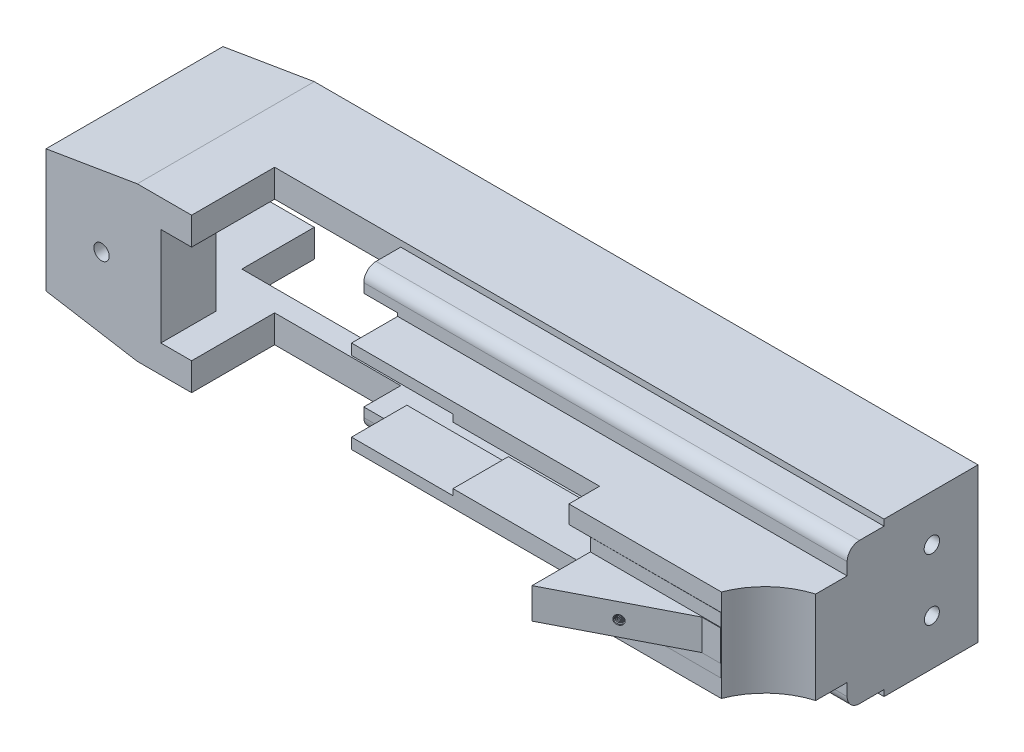
SolidWorks part; units mm, degrees
ref_plane "Front Plane" through (0, 0, 0) normal (0, 0, 1) x (1, 0, 0)
ref_plane "Top Plane" through (0, 0, 0) normal (0, 1, 0) x (1, 0, 0)
ref_plane "Right Plane" through (0, 0, 0) normal (1, 0, 0) x (0, 0, -1)
sketch "Sketch1" plane through (0, 0, 0) normal (0, 0, 1) x (1, 0, 0)
  line L0 (0, 0) -> (245.5, 0)
  line L1 (245.5, 0) -> (245.5, 50)
  line L2 (245.5, 50) -> (0, 50)
  line L3 (0, 50) -> (0, 0)
  dimension "D1" = 245.5
  dimension "D2" = 50
extrude "Boss-Extrude1" add sketch "Sketch1" along normal blind 57.55
sketch "Sketch2" plane through (0, 0, 0) normal (0, 0, -1) x (-1, 0, 0)
  line L0 (0, 9) -> (-205, 9)
  line L1 (0, 50) -> (0, 0) construction
  line L2 (-205, 9) -> (-205, 41)
  line L3 (-205, 41) -> (0, 41)
  line L4 (0, 41) -> (0, 9)
  line L5 (0, 0) -> (-245.5, 0) construction
  line L6 (-245.5, 50) -> (0, 50) construction
  dimension "D1" = 9
  dimension "D2" = 9
  dimension "D3" = 205
extrude "Cut-Extrude1" cut sketch "Sketch2" against normal blind 39.55
sketch "Sketch3" plane through (0, 0, 39.55) normal (0, 0, -1) x (-1, 0, 0)
  line L0 (-10, 9) -> (0, 9)
  line L1 (-205, 9) -> (0, 9) construction
  line L2 (0, 9) -> (0, 41)
  line L3 (0, 41) -> (-10, 41)
  line L4 (0, 41) -> (-205, 41) construction
  line L5 (-10, 41) -> (-10, 9)
  dimension "D1" = 10
extrude "Cut-Extrude2" cut sketch "Sketch3" against normal blind 5
sketch "Sketch4" plane through (0, 0, 39.55) normal (0, 0, -1) x (-1, 0, 0)
  line L0 (0, 9) -> (0, 41) construction
  line L1 (-205, 9) -> (-10, 9) construction
  circle A0 centre (-18.055, 25) radius 2.4875
  dimension "D1" = 4.975
  dimension "D2" = 18.055
  dimension "D3" = 16
extrude "Cut-Extrude3" cut sketch "Sketch4" against normal through all
sketch "Sketch5" plane through (0, 0, 0) normal (0, 0, -1) x (-1, 0, 0)
  line L1 (0, 50) -> (0, 41) construction
  line L4 (0, 45.028) -> (-29.689, 50)
  line L5 (-245.5, 50) -> (0, 50) construction
  line L7 (0, 45.028) -> (0, 51.6223)
  line L8 (0, 51.6223) -> (-29.689, 51.6223)
  line L9 (-29.689, 51.6223) -> (-29.689, 50)
extrude "Cut-Extrude4" cut sketch "Sketch5" against normal through all
sketch "Sketch6" plane through (0, 0, 0) normal (0, 0, -1) x (-1, 0, 0)
  line L1 (0, 9) -> (0, 0) construction
  line L4 (0, 4.972) -> (-29.689, 0)
  line L5 (0, 0) -> (-245.5, 0) construction
  line L7 (-29.689, 0) -> (0.6137, 0)
  line L8 (0.6137, 0) -> (0.6137, 4.972)
  line L9 (0.6137, 4.972) -> (0, 4.972)
extrude "Cut-Extrude5" cut sketch "Sketch6" against normal through all
sketch "Sketch7" plane through (0, 0, 0) normal (0, 0, -1) x (-1, 0, 0)
  line L0 (-29.689, 0) -> (-29.689, 9)
  line L1 (-29.689, 0) -> (-245.5, 0) construction
  line L2 (-205, 9) -> (0, 9) construction
  line L3 (0, 9) -> (0, 4.972) construction
  line L4 (-29.689, 9) -> (-112, 9)
  line L5 (-112, 9) -> (-112, 0)
  line L6 (-112, 0) -> (-29.689, 0)
  point P8 (-112, 4.5)
  dimension "D1" = 29.689
  dimension "D2" = 82.311
extrude "Cut-Extrude6" cut sketch "Sketch7" against normal blind 23.55
sketch "Sketch8" plane through (0, 0, 39.55) normal (0, 0, -1) x (-1, 0, 0)
  line L0 (-37.342, 9) -> (-37.342, 41)
  line L1 (-205, 9) -> (-10, 9) construction
  line L2 (-10, 41) -> (-205, 41) construction
  line L3 (0, 9) -> (0, 41) construction
  line L4 (-37.342, 9) -> (-99.342, 9)
  line L5 (-99.342, 9) -> (-99.342, 41)
  line L6 (-99.342, 41) -> (-37.342, 41)
  dimension "D1" = 37.342
  dimension "D2" = 62
extrude "Cut-Extrude7" cut sketch "Sketch8" against normal through all
sketch "Sketch9" plane through (0, 0, 39.55) normal (0, 0, -1) x (-1, 0, 0)
  line L0 (-99.342, 13.5) -> (-132.342, 13.5)
  line L1 (-99.342, 41) -> (-99.342, 9) construction
  line L2 (-132.342, 13.5) -> (-132.342, 36.5)
  line L3 (-132.342, 36.5) -> (-99.342, 36.5)
  line L4 (-99.342, 36.5) -> (-99.342, 13.5)
  line L5 (-205, 9) -> (-99.342, 9) construction
  line L6 (-99.342, 41) -> (-205, 41) construction
  dimension "D1" = 4.5
  dimension "D2" = 4.5
  dimension "D3" = 33
extrude "Cut-Extrude8" cut sketch "Sketch9" against normal through all
sketch "Sketch10" plane through (0, 0, 39.55) normal (0, 0, -1) x (-1, 0, 0)
  line L0 (-132.342, 34.196) -> (-184.342, 34.196)
  line L1 (-132.342, 36.5) -> (-132.342, 13.5) construction
  line L2 (-184.342, 34.196) -> (-184.342, 15.499)
  line L3 (-184.342, 15.499) -> (-132.342, 15.499)
  line L4 (-132.342, 15.499) -> (-132.342, 34.196)
  line L5 (-205, 9) -> (-99.342, 9) construction
  line L6 (-99.342, 41) -> (-205, 41) construction
  dimension "D1" = 6.499
  dimension "D2" = 6.804
  dimension "D3" = 52
extrude "Cut-Extrude9" cut sketch "Sketch10" against normal through all
sketch "Sketch11" plane through (0, 0, 39.55) normal (0, 0, -1) x (-1, 0, 0)
  line L0 (-184.342, 15.499) -> (-187.342, 15.499)
  line L1 (-187.342, 15.499) -> (-187.342, 34.2927)
  line L2 (-187.342, 34.2927) -> (-184.342, 34.196)
  line L3 (-184.342, 34.196) -> (-184.342, 15.499)
  dimension "D1" = 3
extrude "Cut-Extrude10" cut sketch "Sketch11" against normal blind 3
sketch "Sketch12" plane through (0, 50, 0) normal (0, 1, 0) x (1, 0, 0)
  line L0 (47.342, -57.55) -> (47.342, -30.55)
  line L1 (245.5, -57.55) -> (29.689, -57.55) construction
  line L2 (0, -57.55) -> (0, 0) construction
  line L3 (47.342, -30.55) -> (88.342, -30.55)
  line L4 (88.342, -30.55) -> (88.342, -57.55)
  line L5 (88.342, -57.55) -> (47.342, -57.55)
  point P7 (88.342, -44.05)
  dimension "D1" = 47.342
  dimension "D2" = 41
  dimension "D3" = 27
extrude "Cut-Extrude11" cut sketch "Sketch12" against normal through all
sketch "Sketch13" plane through (0, 50, 0) normal (0, 1, 0) x (1, 0, 0)
  line L0 (88.342, -57.55) -> (88.342, -42.55)
  line L1 (88.342, -57.55) -> (88.342, -30.55) construction
  line L2 (88.342, -42.55) -> (99.342, -42.55)
  line L3 (99.342, -42.55) -> (99.342, -57.55)
  line L4 (245.5, -57.55) -> (88.342, -57.55) construction
  line L5 (99.342, -57.55) -> (88.342, -57.55)
  dimension "D1" = 15
  dimension "D2" = 11
extrude "Cut-Extrude12" cut sketch "Sketch13" against normal through all
sketch "Sketch14" plane through (0, 50, 0) normal (0, 1, 0) x (1, 0, 0)
  line L0 (99.342, -57.55) -> (99.342, -42.55)
  line L1 (99.342, -42.55) -> (245.5, -42.55)
  line L2 (245.5, -57.55) -> (245.5, 0) construction
  line L3 (245.5, -42.55) -> (245.5, -57.55)
  line L4 (245.5, -57.55) -> (99.342, -57.55)
extrude "Cut-Extrude13" cut sketch "Sketch14" against normal blind 10
sketch "Sketch15" plane through (0, 40, 0) normal (0, 1, 0) x (1, 0, 0)
  line L0 (180, -57.55) -> (180, -86.52)
  line L1 (99.342, -57.55) -> (245.5, -57.55) construction
  line L2 (180, -86.52) -> (245.5, -86.52)
  line L3 (245.5, -86.52) -> (245.5, -57.55)
  line L4 (245.5, -57.55) -> (180, -57.55)
  line L5 (0, -57.55) -> (0, 0) construction
  dimension "D1" = 28.97
  dimension "D2" = 180
extrude "Boss-Extrude2" add sketch "Sketch15" against normal blind 30
sketch "Sketch17" plane through (0, 40, 0) normal (0, 1, 0) x (1, 0, 0)
  line L0 (180, -67.55) -> (187, -67.55)
  line L1 (180, -57.55) -> (180, -86.52) construction
  line L2 (99.342, -57.55) -> (180, -57.55) construction
  line L3 (187, -67.55) -> (187, -86.52)
  line L4 (180, -86.52) -> (245.5, -86.52) construction
  line L5 (187, -86.52) -> (180, -86.52)
  line L6 (180, -86.52) -> (180, -67.55)
  dimension "D1" = 10
  dimension "D2" = 7
extrude "Cut-Extrude14" cut sketch "Sketch17" against normal through all
sketch "Sketch18" plane through (0, 0, 57.55) normal (0, 0, -1) x (-1, 0, 0)
  line L0 (-180, 15.499) -> (-184.342, 15.499)
  line L1 (-184.342, 15.499) -> (-184.342, 34.196)
  line L2 (-184.342, 34.196) -> (-180, 34.196)
  line L3 (-180, 34.196) -> (-180, 15.499)
extrude "Cut-Extrude15" cut sketch "Sketch18" against normal through all
sketch "Sketch20" plane through (0, 0, 67.55) normal (0, 0, 1) x (1, 0, 0)
  line L0 (184.342, 34.196) -> (187, 34.196)
  line L1 (187, 10) -> (187, 40) construction
  line L2 (184.342, 34.196) -> (184.342, 15.499)
  line L3 (184.342, 15.499) -> (187, 15.499)
  line L4 (187, 15.499) -> (187, 34.196)
extrude "Cut-Extrude16" cut sketch "Sketch20" against normal blind 18
sketch "Sketch21" plane through (0, 40, 0) normal (0, 1, 0) x (1, 0, 0)
  line L1 (245.5, -86.52) -> (245.5, -42.55) construction
  line L2 (245.5, -67.597) -> (245.5, -86.52)
  line L3 (245.5, -86.52) -> (187, -86.52)
  line L5 (245.5, -67.597) -> (187, -67.55)
  line L7 (187, -67.55) -> (176.1532, -67.55)
  line L8 (176.1532, -67.55) -> (176.1532, -86.52)
  line L9 (176.1532, -86.52) -> (187, -86.52)
  dimension "D1" = 18.923
extrude "Cut-Extrude17" cut sketch "Sketch21" against normal blind 10
sketch "Sketch27" plane through (0, 40, 0) normal (0, 1, 0) x (1, 0, 0)
  line L1 (180, -57.55) -> (180, -67.55) construction
  line L2 (180, -67.519) -> (245.5, -67.519)
  line L3 (245.5, -67.597) -> (245.5, -42.55) construction
  line L4 (187, -67.55) -> (180, -67.55) construction
  line L5 (180, -67.519) -> (180, -67.55)
  line L6 (180, -67.55) -> (245.5, -67.597)
  line L7 (245.5, -67.597) -> (245.5, -67.519)
  dimension "D1" = 0.031
extrude "Cut-Extrude21" cut sketch "Sketch27" against normal blind 5.804
sketch "Sketch22" plane through (0, 10, 0) normal (0, -1, 0) x (1, 0, 0)
  line L0 (187, 67.55) -> (245.5, 67.55)
  line L1 (245.5, 86.52) -> (245.5, 57.55) construction
  line L2 (245.5, 67.55) -> (245.5, 86.52)
  line L3 (245.5, 86.52) -> (187, 86.52)
  line L4 (187, 86.52) -> (187, 67.55)
extrude "Cut-Extrude18" cut sketch "Sketch22" against normal blind 10
sketch "Sketch23" plane through (0, 30, 0) normal (0, 1, 0) x (1, 0, 0)
  line L9 (187, -67.55) -> (187, -86.52) construction
  line L12 (223.471, -67.772) -> (187, -86.52)
  line L13 (223.471, -67.772) -> (245.5, -67.772)
  line L14 (187, -86.52) -> (245.5, -86.52)
  line L15 (245.5, -86.52) -> (245.5, -67.772)
  dimension "D2" = 36.471
extrude "Cut-Extrude20" cut sketch "Sketch23" against normal through all
sketch "Sketch29" plane through (74.2658, 0, 144.4713) normal (0.4572, 0, 0.8894) x (0.8894, 0, -0.4572)
  line L0 (126.7571, 20) -> (126.7571, 30) construction
  line L1 (167.7646, 30) -> (126.7571, 30) construction
  circle A0 centre (147.7571, 24.882) radius 1.5
  dimension "D3" = 3
  dimension "D1" = 21
  dimension "D2" = 5.118
extrude "Cut-Extrude22" cut sketch "Sketch29" against normal blind 8.5
sketch "Sketch31" plane through (0, 0, 0) normal (0, -1, 0) x (1, 0, 0)
  line L0 (88.342, 30.55) -> (245.5, 30.55)
  line L2 (245.5, 57.55) -> (245.5, 0) construction
  line L3 (245.5, 30.55) -> (245.5, 57.55)
  line L4 (245.5, 57.55) -> (99.342, 57.55)
  line L5 (99.342, 57.55) -> (88.342, 57.55)
  line L6 (88.342, 57.55) -> (88.342, 30.55)
extrude "Cut-Extrude23" cut sketch "Sketch31" against normal blind 2
sketch "Sketch32" plane through (0, 2, 0) normal (0, -1, 0) x (1, 0, 0)
  line L0 (99.342, 42.55) -> (245.5, 42.55)
  line L1 (245.5, 30.55) -> (245.5, 57.55) construction
  line L2 (245.5, 42.55) -> (245.5, 57.55)
  line L3 (245.5, 57.55) -> (99.342, 57.55)
  line L4 (99.342, 57.55) -> (99.342, 42.55)
extrude "Cut-Extrude24" cut sketch "Sketch32" against normal blind 8
fillet "Fillet2" radius 4 1 edges at (166.921, 2, 42.55)
sketch "Sketch35" plane through (0, 0, 67.55) normal (0, 0, 1) x (1, 0, 0)
  line L0 (245.5, 20) -> (245.5, 15.797)
  line L1 (245.5, 15.797) -> (187, 15.797)
  line L2 (187, 20) -> (187, 15.499) construction
  line L3 (187, 15.797) -> (187, 20)
  line L4 (187, 20) -> (245.5, 20)
extrude "Boss-Extrude4" add sketch "Sketch35" along normal blind 0.08
sketch "Sketch37" plane through (0, 50, 0) normal (0, 1, 0) x (1, 0, 0)
  line L0 (88.342, -30.55) -> (245.5, -30.55)
  line L1 (245.5, -42.55) -> (245.5, 0) construction
  line L2 (245.5, -30.55) -> (245.5, -42.55)
  line L3 (245.5, -42.55) -> (88.342, -42.55) construction
  line L4 (245.5, -42.55) -> (88.342, -42.55)
  line L5 (88.342, -42.55) -> (88.342, -30.55)
extrude "Cut-Extrude25" cut sketch "Sketch37" against normal blind 2
fillet "Fillet3" radius 4 1 edges at (166.921, 48, 42.55)
sketch "Sketch38" plane through (205, 0, 0) normal (-1, 0, 0) x (0, 0, 1)
  line L0 (30.55, 0) -> (0, 0) construction
  line L1 (30.55, 50) -> (0, 50) construction
  line L2 (0, 41) -> (0, 9) construction
  circle A0 centre (15, 15) radius 2.4445
  circle A1 centre (15, 35) radius 2.5019
  dimension "D1" = 15
  dimension "D2" = 15
  dimension "D3" = 15
  dimension "D4" = 15
extrude "Cut-Extrude26" cut sketch "Sketch38" against normal through all
sketch "Sketch39" plane through (0, 0, 67.772) normal (0, 0, 1) x (1, 0, 0)
  line L0 (229.571, 20) -> (229.571, 30)
  line L1 (223.471, 20) -> (245.5, 20) construction
  line L2 (245.5, 30) -> (223.471, 30) construction
  line L3 (223.471, 20) -> (223.471, 30) construction
  line L4 (229.571, 20) -> (229.571, 12.2217)
  line L6 (253.2973, 12.2217) -> (254.0062, 41.842)
  line L7 (254.0062, 41.842) -> (229.571, 41.842)
  line L8 (229.571, 41.842) -> (229.571, 30)
  line L9 (229.571, 12.2217) -> (229.571, 4.0695)
  line L10 (229.571, 4.0695) -> (253.2973, 4.0695)
  line L11 (253.2973, 4.0695) -> (253.2973, 12.2217)
  dimension "D1" = 6.1
extrude "Cut-Extrude27" cut sketch "Sketch39" against normal blind 15
sketch "Sketch42" plane through (0, 10, 0) normal (0, -1, 0) x (1, 0, 0)
  line L0 (229.571, 67.55) -> (229.571, 52.772)
  line L1 (229.571, 52.772) -> (245.5, 52.772)
  arc A0 (245.5, 52.772) -> (229.571, 67.55) centre (252.4707, 76.2594) cw
  dimension "D1" = 24.5
extrude "Boss-Extrude5" add sketch "Sketch42" against normal blind 30
thread "Thread1" pitch 0.5 method extrude profile "Thread Profile2" start angle 0, offset 0, length 6.5, pitch 0.5, diameter 3
ref_plane "Plane2" through (204.3428, 24.882, 77.6049) normal (0, -1, 0) x (-0.8894, 0, 0.4572)
sketch "Thread Profile2" plane through (204.3428, 24.882, 77.6049) normal (0, -1, 0) x (-0.8894, 0, 0.4572)
  line L0 (0, 0) -> (0, 0.5) construction
  line L11 (0, 0) -> (0, 0.4375)
  line L12 (0, 0.4375) -> (-0.2706, 0.2812)
  line L13 (-0.2706, 0.2812) -> (-0.2706, 0.1562)
  line L15 (-0.2706, 0.1562) -> (0, 0)
  line L17 (-0.2706, 0.2187) -> (0, 0.2187) construction
  point P2 (0, 0)
  dimension "Pitch" = 0.5
  dimension "Profile_Angle" = 60
  dimension "Profile_Land" = 0.125
  dimension "Profile_Height" = 0.2706
